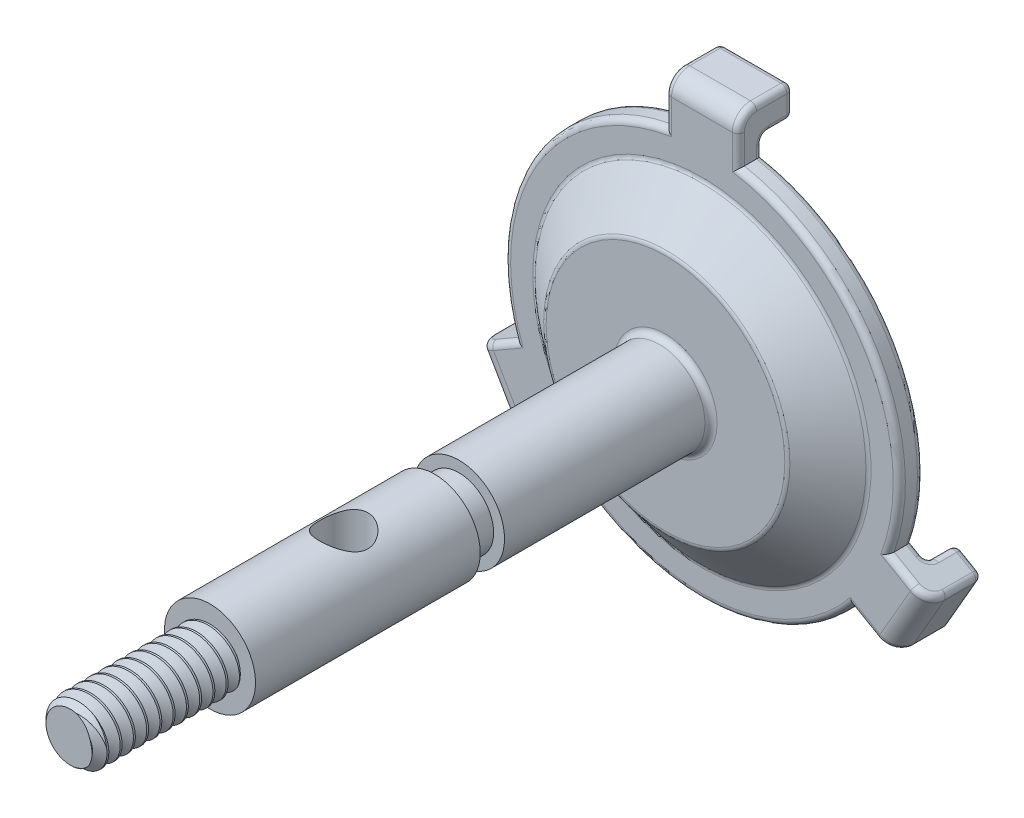
SolidWorks part; units mm, degrees
material "Plain Carbon Steel"
ref_plane "Front Plane" through (0, 0, 0) normal (0, 0, 1) x (1, 0, 0)
ref_plane "Top Plane" through (0, 0, 0) normal (0, 1, 0) x (1, 0, 0)
ref_plane "Right Plane" through (0, 0, 0) normal (1, 0, 0) x (0, 0, -1)
sketch "Sketch1" plane through (0, 0, 0) normal (1, 0, 0) x (0, 0, -1)
  line L0 (-9.1498, 0) -> (7.2508, 0) construction
  line L1 (0.889, 2.286) -> (3.81, 2.286)
  line L2 (2.413, 8.255) -> (1.397, 8.255)
  line L3 (1.397, 8.255) -> (1.397, 6.985)
  line L4 (1.397, 6.985) -> (-0.127, 5.08)
  line L5 (-0.127, 5.08) -> (-0.127, 1.905)
  line L6 (2.413, 6.985) -> (0.889, 5.08)
  line L7 (0.889, 5.08) -> (0.889, 2.286)
  line L8 (3.81, 2.286) -> (3.81, 0)
  line L9 (2.413, 6.985) -> (2.413, 8.255)
  line L10 (3.81, 0) -> (0, 0)
  line L11 (-9.779, 1.905) -> (-19.177, 1.905)
  line L12 (0, 0) -> (-25.019, 0)
  line L14 (-0.127, 1.905) -> (-8.763, 1.905)
  line L15 (-25.019, 0) -> (-25.019, 1.27)
  line L17 (-8.763, 1.905) -> (-8.763, 1.4478)
  line L18 (-8.763, 1.4478) -> (-9.779, 1.4478)
  line L19 (-9.779, 1.905) -> (-9.779, 1.4478)
  line L21 (-19.177, 1.905) -> (-19.177, 1.27)
  line L22 (-19.177, 1.27) -> (-25.019, 1.27)
  dimension "D1" = 8.255
  dimension "D2" = 6.985
  dimension "D3" = 5.08
  dimension "D4" = 2.54
  dimension "D5" = 1.016
  dimension "D6" = 1.016
  dimension "D7" = 3.937
  dimension "D8" = 2.286
  dimension "D9" = 8.636
  dimension "D10" = 1.905
  dimension "D11" = 1.27
  dimension "D12" = 5.842
  dimension "D13" = 9.398
  dimension "D14" = 1.016
  dimension "D15" = 1.4478
revolve "Base revolve" add sketch "Sketch1" angle 360 about L0
sketch "Sketch2" plane through (0, 0, -2.413) normal (0, 0, -1) x (-1, 0, 0)
  line L0 (0, 0) -> (0, 11.1377) construction
  line L2 (-1.524, 10.0943) -> (1.524, 10.0943)
  line L3 (-1.524, 10.0943) -> (-1.524, 8.1131)
  line L4 (-1.524, 8.1131) -> (1.524, 8.1131)
  line L5 (1.524, 10.0943) -> (1.524, 8.1131)
  line L6 (-1.524, 10.0943) -> (1.524, 8.1131) construction
  line L7 (-1.524, 8.1131) -> (1.524, 10.0943) construction
  circle A0 centre (0, 0) radius 8.255 construction
  point P3 (0, 9.1037)
  dimension "D1" = 3.048
  dimension "D2" = 1.9812
extrude "Flange A" add sketch "Sketch2" against normal up to surface (1.016 mm away) up to face at (6.985, 0, -1.397)
sketch "Sketch3" plane through (0, 0, -2.413) normal (0, 0, -1) x (-1, 0, 0)
  line L0 (-1.524, 10.0943) -> (-1.524, 8.1131) construction
  line L1 (-1.524, 8.8243) -> (1.524, 8.8243)
  line L2 (-1.524, 8.8243) -> (-1.524, 10.0943)
  line L3 (-1.524, 10.0943) -> (1.524, 10.0943)
  line L4 (1.524, 8.8243) -> (1.524, 10.0943)
  line L5 (-1.524, 8.8243) -> (1.524, 10.0943) construction
  line L6 (-1.524, 10.0943) -> (1.524, 8.8243) construction
  point P0 (0, 9.4593)
  dimension "D1" = 1.27
extrude "Flange B" add sketch "Sketch3" along normal blind 1.27
pattern_circular "Circular pattern for flanges" count 3 over 360 about axis through (0, 0, -2.413) along (0, 0, 1) of "Flange A", "Flange B"
sketch "Sketch4" plane through (0, 0, 0) normal (0, 1, 0) x (1, 0, 0)
  line L0 (1.905, -9.779) -> (-1.905, -9.779) construction
  line L1 (0, -13.589) -> (0, 0) construction
  circle A0 centre (0, -13.589) radius 1.016
  dimension "D1" = 2.032
  dimension "D2" = 3.81
extrude "Shaft hole" cut sketch "Sketch4" against normal through all both and the other way through all
sketch "Sketch6" plane through (0, 0, 19.177) normal (0, 0, 1) x (1, 0, 0)
  circle A0 centre (0, 0) radius 1.27
  circle A1 centre (0, 0) radius 1.27 construction
curve "Helix/Spiral1" pitch 0.5542 height 6.096 radius 1.27 centre (0, 0, 19.177) axis (0, 0, 1) start towards (-1, 0, 0)
ref_point "Point1" parameters "D1"=0
sketch "Sketch7" plane through (0, 0, 0) normal (0, 1, 0) x (1, 0, 0)
  line L0 (-1.27, -25.0349) -> (-0.8851, -25.2571)
  line L1 (-0.8851, -25.2571) -> (-0.8851, -25.2889)
  line L2 (-1.27, -25.0349) -> (-1.27, -25.5111)
  line L3 (-0.8851, -25.2889) -> (-1.27, -25.5111)
  line L4 (-1.0775, -25.146) -> (-1.0775, -25.4) construction
  line L5 (-1.27, -25.273) -> (-0.8851, -25.273) construction
  line L6 (-1.27, -19.177) -> (-1.27, -25.019) construction
  dimension "D2" = 60
  dimension "D1" = 0.254
  dimension "D3" = 0.0317
chamfer "Tip chamfer" distance 0.254 angle 45 1 edges at (1.27, 0, 25.019)
sweep "Thread cut" cut profiles "Sketch7" path "Helix/Spiral1" align with end faces yes
fillet "Flange fillets" radius 0.762 3 edges at (-8.7419, -5.0472, -1.397) (8.7419, -5.0472, -1.397) (0, 10.0943, -1.397)
fillet "Surface fillet" radius 0.254 55 edges at (8.4041, -3.0923, -3.048) (-8.4041, -3.0923, -3.048) (-6.8801, -5.732, -3.048) (6.8801, -5.732, -3.048) (-1.524, 10.0943, -2.921) (-1.524, 9.8711, -1.6202) (1.524, 10.0943, -2.921) (1.524, 9.8711, -1.6202) (9.5039, -3.7273, -2.921) (9.3106, -3.6157, -1.6202) (7.9799, -6.367, -2.921) (7.7866, -6.2554, -1.6202) (-7.9799, -6.367, -2.921) (-7.7866, -6.2554, -1.6202) (-9.5039, -3.7273, -2.921) (-9.3106, -3.6157, -1.6202) (1.905, 0, 0.127) (5.08, 0, 0.127) (-7.149, 4.1275, -1.397) (-1.524, 8.7227, -1.397) (1.524, 8.7227, -1.397) (7.149, 4.1275, -1.397) (8.3161, -3.0415, -1.397) (6.7921, -5.6812, -1.397) (0, -8.255, -1.397) (-6.7921, -5.6812, -1.397) (-8.3161, -3.0415, -1.397) (6.985, 0, -1.397) (0, 8.8243, -3.683) (1.524, 9.4593, -3.683) (0, 10.0943, -3.683) (-1.524, 9.4593, -3.683) (-7.6421, -4.4122, -3.683) (-8.954, -3.4098, -3.683) (-8.7419, -5.0472, -3.683) (-7.43, -6.0495, -3.683) (7.6421, -4.4122, -3.683) (7.43, -6.0495, -3.683) (8.7419, -5.0472, -3.683) (8.954, -3.4098, -3.683) (8.0961, -2.9145, -2.413) (7.149, 4.1275, -2.413) (-7.149, 4.1275, -2.413) (-8.0961, -2.9145, -2.413) (-7.6421, -4.4122, -2.413) (-6.5721, -5.5542, -2.413) (0, -8.255, -2.413) (6.5721, -5.5542, -2.413) (7.6421, -4.4122, -2.413) (6.985, 0, -2.413)
